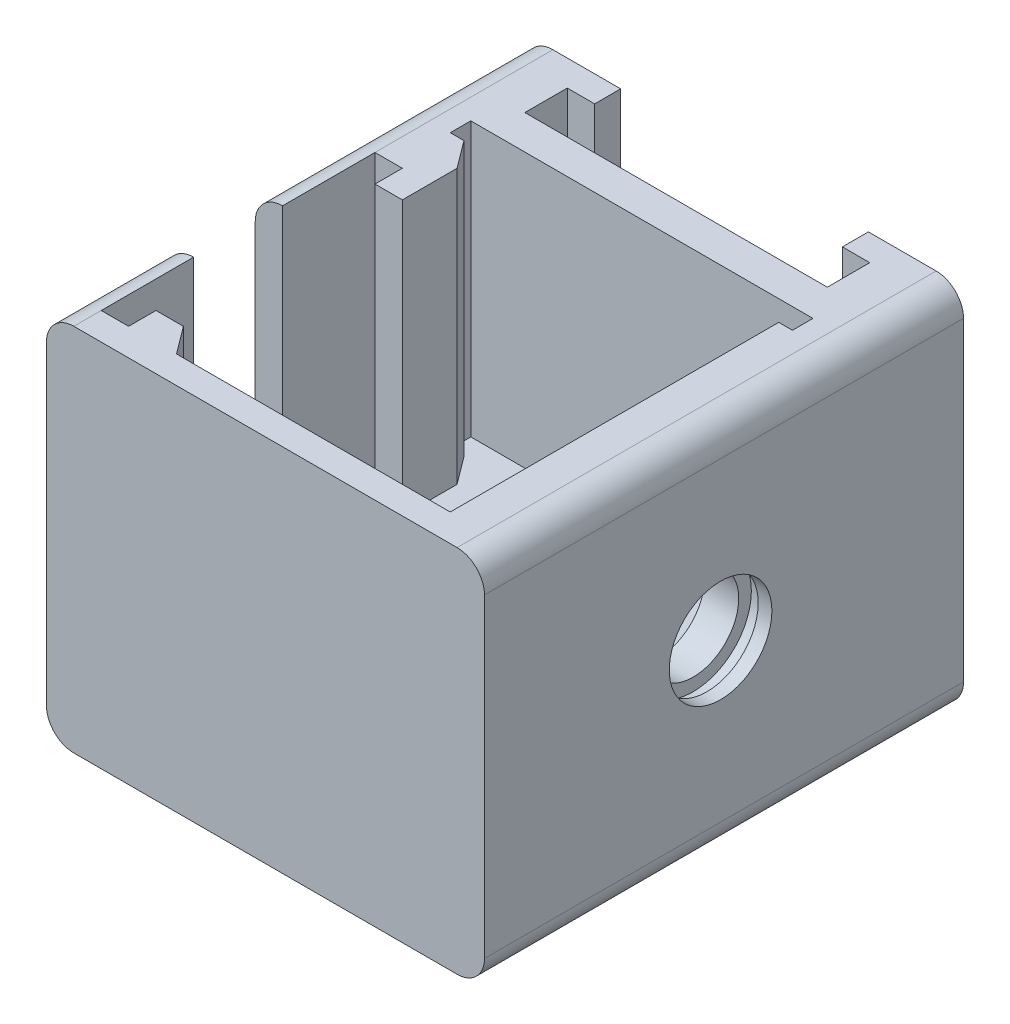
SolidWorks part; units mm, degrees
material "UNOBTANIUM"
ref_plane "Top Plane" through (0, 0, 0) normal (0, 0, 1) x (1, 0, 0)
ref_plane "Right Plane" through (0, 0, 0) normal (0, 1, 0) x (1, 0, 0)
ref_plane "Front Plane" through (0, 0, 0) normal (1, 0, 0) x (0, 0, -1)
ref_axis "x-axis" through (-17.6, 0, 0) along (1, 0, 0)
ref_axis "y-axis" through (0, -14.85, 0) along (0, 1, 0)
ref_axis "z-axis" through (0, 0, 36.75) along (0, 0, -1)
sketch "Sketch1" plane through (0, 0, 0) normal (0, 0, 1) x (1, 0, 0)
  line L1 (-16, 13.5) -> (16, 13.5)
  line L2 (-16, 13.5) -> (-16, -13.5)
  line L3 (-16, -13.5) -> (16, -13.5)
  line L4 (16, 13.5) -> (16, -13.5)
  line L5 (-16, 13.5) -> (16, -13.5) construction
  line L6 (-16, -13.5) -> (16, 13.5) construction
  point P0 (0, 0)
  dimension "D1" = 32
  dimension "D2" = 27
extrude "Boss-Extrude1" add sketch "Sketch1" along normal blind 35
fillet "Fillet1" radius 2 4 edges at (16, -13.5, 17.5) (16, 13.5, 17.5) (-16, -13.5, 17.5) (-16, 13.5, 17.5)
sketch "Sketch2" plane through (0, -13.5, 0) normal (0, -1, 0) x (1, 0, 0)
  line L0 (-9.05, 0) -> (-9.05, 1.9)
  line L1 (-14, 0) -> (14, 0) construction
  line L2 (-9.05, 1.9) -> (-11.05, 1.9)
  line L3 (-11.05, 1.9) -> (-11.05, 5)
  line L4 (-11.05, 5) -> (11.05, 5)
  line L5 (11.05, 5) -> (11.05, 1.9)
  line L6 (11.05, 1.9) -> (9.05, 1.9)
  line L7 (9.05, 1.9) -> (9.05, 0)
  line L9 (-9.05, 0) -> (9.05, 0)
  point P4 (0, 0)
  dimension "D1" = 18.1
  dimension "D2" = 1.9
  dimension "D3" = 3.1
  dimension "D4" = 22.1
extrude "Cut-Extrude1" cut sketch "Sketch2" against normal through all both and the other way through all
sketch "Sketch3" plane through (0, -13.5, 0) normal (0, -1, 0) x (1, 0, 0)
  line L0 (-9.05, 0) -> (-9.05, 1.9)
  line L1 (-9.05, 1.9) -> (-11.05, 1.9)
  line L2 (-11.05, 1.9) -> (-11.05, 5)
  line L3 (-11.05, 5) -> (11.05, 5)
  line L4 (11.05, 5) -> (11.05, 1.9)
  line L5 (11.05, 1.9) -> (9.05, 1.9)
  line L6 (9.05, 1.9) -> (9.05, 0)
  line L7 (9.05, 0) -> (-9.05, 0)
extrude "Boss-Extrude2" add sketch "Sketch3" against normal blind 7
sketch "Sketch4" plane through (0, 0, 1.9) normal (0, 0, -1) x (-1, 0, 0)
  line L1 (-9.05, 6.5) -> (-9.05, 5.5)
  line L2 (-9.05, 13.5) -> (-9.05, -6.5) construction
  arc A0 (-9.05, 6.5) -> (-9.05, 5.5) centre (-9.425, 6) cw
  dimension "D1" = 0.625
  dimension "D2" = 0.25
  dimension "D3" = 7
extrude "Boss-Extrude3" add sketch "Sketch4" along normal up to surface (1.9 mm away) up to face at (0, 1.1667, 0)
mirror "Mirror1" about plane through (0, 0, 0) normal (1, 0, 0) of "Boss-Extrude3"
sketch "Sketch5" plane through (0, 0, 0) normal (0, 0, -1) x (-1, 0, 0)
  line L0 (9.05, -6.5) -> (-9.05, -6.5) construction
  line L1 (-1, -6.5) -> (1, -6.5)
  line L2 (-1, -6.5) -> (-1, -13.5)
  line L3 (-1, -13.5) -> (1, -13.5)
  line L4 (1, -6.5) -> (1, -13.5)
  line L5 (14, -13.5) -> (-14, -13.5) construction
  point P8 (0, -6.5)
  dimension "D1" = 2
extrude "Cut-Extrude2" cut sketch "Sketch5" against normal offset from surface (33 mm away) 2 up to face at (0, 0, 35)
sketch "Sketch6" plane through (0, 13.5, 0) normal (0, 1, 0) x (1, 0, 0)
  line L0 (-12.5, -7.5) -> (-12.5, -9)
  line L1 (-12.5, -9) -> (-11.5, -9)
  line L2 (-11.5, -9) -> (-11.5, -33)
  line L3 (-11.5, -33) -> (11.5, -33)
  line L4 (11.5, -33) -> (11.5, -9)
  line L5 (11.5, -9) -> (12.5, -9)
  line L6 (12.5, -9) -> (12.5, -7.5)
  line L7 (12.5, -7.5) -> (-12.5, -7.5)
  line L8 (11.05, -5) -> (-11.05, -5) construction
  line L9 (0, -7.5) -> (0, -5) construction
  line L10 (14, -35) -> (-14, -35) construction
  dimension "D1" = 2.5
  dimension "D2" = 1.5
  dimension "D3" = 1
  dimension "D4" = 25
  dimension "D5" = 2
extrude "Cut-Extrude3" cut sketch "Sketch6" against normal up to surface (20 mm away) up to face at (7.0333, -6.5, 2.3)
sketch "Sketch7" plane through (0, -13.5, 0) normal (0, -1, 0) x (1, 0, 0)
  line L0 (1, 0) -> (14, 0) construction
  line L1 (1, 0) -> (-1, 0)
  line L2 (1, 0) -> (1, 33)
  line L3 (1, 33) -> (-1, 33)
  line L4 (-1, 0) -> (-1, 33)
  line L5 (1, 33) -> (1, 0) construction
extrude "Boss-Extrude4" add sketch "Sketch7" against normal blind 0.25
fillet "Fillet2" radius 6 1 edges at (0, -13.25, 33)
ref_axis "Axis1" through (63.07, 0, 17.75) along (-1, 0, 0)
ref_plane "Plane1" through (0, 0, 17.75) normal (0, 0, -1) x (-1, 0, 0)
sketch "Sketch9" plane through (0, 0, 17.75) normal (0, 0, -1) x (-1, 0, 0)
  line L0 (-15, 4.25) -> (-14, 4.25)
  line L1 (-16, -11.5) -> (-16, 11.5) construction
  line L2 (-14, 4.25) -> (-14, 3.325)
  line L3 (-14, 3.325) -> (-11.5, 3.325)
  line L4 (-11.5, 3.325) -> (-11.5, 0)
  line L5 (-63.07, 0) -> (46.93, 0) construction
  line L6 (-11.5, 0) -> (-16, 0)
  line L8 (-16, 0) -> (-0.664, 0) construction
  line L9 (-11.5, -6.5) -> (-11.5, 13.5) construction
  line L10 (-15, 4.25) -> (-15, 3.75)
  line L11 (-15, 3.75) -> (-16, 3.75)
  line L12 (-16, 3.75) -> (-16, 0)
  dimension "D1" = 6.65
  dimension "D2" = 8.5
  dimension "D3" = 1
  dimension "D4" = 1
  dimension "D5" = 7.5
revolve "Cut-Revolve1" cut sketch "Sketch9" angle 360 about L8
sketch "Sketch10" plane through (0, 13.5, 0) normal (0, 1, 0) x (1, 0, 0)
  line L0 (11.5, -31) -> (13.5, -31)
  line L1 (11.5, -9) -> (11.5, -33) construction
  line L2 (13.5, -31) -> (13.5, -33)
  line L3 (13.5, -33) -> (11.5, -33)
  line L4 (11.5, -33) -> (11.5, -31)
  dimension "D1" = 2
  dimension "D2" = 2
extrude "Cut-Extrude4" [suppressed] cut sketch "Sketch10" against normal up to surface (20 mm away)
mirror "Mirror2" [suppressed] about plane through (0, 0, 0) normal (1, 0, 0)
sketch "Sketch11" plane through (-16, 0, 44) normal (1, 0, 0) x (0, 0, -1)
  line L0 (21, 23) -> (21, 0) construction
  line L4 (24.25, 23) -> (24.25, 0)
  line L5 (17.75, 23) -> (17.75, 0)
  line L6 (9, 11.5) -> (44, 11.5) construction
  line L7 (21, 0) -> (44, 0) construction
  line L8 (9, 11.5) -> (9, -11.5) construction
  arc A2 (24.25, 23) -> (17.75, 23) centre (21, 23) ccw
  arc A3 (17.75, 0) -> (24.25, 0) centre (21, 0) ccw
  point P2 (21, 11.5)
  dimension "D1" = 6.5
  dimension "D2" = 12
extrude "Cut-Extrude5" cut sketch "Sketch11" along normal up to surface (4.5 mm away) up to face at (-11.5, 3.5, 21)
sketch "Sketch14" plane through (0, 13.5, 0) normal (0, 1, 0) x (1, 0, 0)
  line L0 (-11.5, -9) -> (-11.5, -19.75) construction
  line L1 (-11.5, -13) -> (-14, -13)
  line L2 (-11.5, -13) -> (-11.5, -33)
  line L3 (-11.5, -33) -> (-14, -33)
  line L4 (-14, -13) -> (-14, -33)
  line L5 (-16, -35) -> (-16, -26.25) construction
  line L6 (-11.5, -26.25) -> (-11.5, -19.75) construction
  point P12 (-11.5, -23)
  dimension "D1" = 2
extrude "Cut-Extrude6" cut sketch "Sketch14" against normal up to surface (20 mm away) up to face at (-8.3333, -6.5, 16.5)
sketch "Sketch16" plane through (0, 13.5, 0) normal (0, 1, 0) x (1, 0, 0)
  line L1 (-12, -11) -> (-10, -11)
  line L2 (-12, -11) -> (-12, -15)
  line L3 (-12, -15) -> (-10, -15)
  line L4 (-10, -11) -> (-10, -15)
  line L5 (-14, -33) -> (-14, -13) construction
  line L6 (-12, -33) -> (-12, -31)
  line L7 (-14, -33) -> (11.5, -33) construction
  line L8 (-12, -31) -> (-10, -31)
  line L9 (-10, -31) -> (-10, -33)
  line L10 (-10, -33) -> (-12, -33)
  line L11 (-12.5, -9) -> (-11.5, -9) construction
  line L13 (-11.5, -13) -> (-14, -13) construction
  line L14 (-14, -13) -> (-14, -19.75) construction
  dimension "D1" = 4
  dimension "D2" = 2
  dimension "D3" = 2
  dimension "D4" = 2
  dimension "D5" = 2
extrude "Boss-Extrude5" add sketch "Sketch16" against normal up to surface (20 mm away) up to face at (8.3333, -6.5, 16.5)
sketch "Sketch20" plane through (0, 13.5, 0) normal (0, 1, 0) x (1, 0, 0)
  line L0 (-11.5, -9) -> (-10, -11)
  line L1 (-10, -11) -> (-11.5, -11)
  line L2 (-11.5, -11) -> (-11.5, -9)
  line L3 (-10, -31) -> (-8.5, -33)
  line L4 (-1, -33) -> (-10, -33) construction
  line L5 (-8.5, -33) -> (-10, -33)
  line L6 (-10, -33) -> (-10, -31)
extrude "Boss-Extrude6" add sketch "Sketch20" against normal up to surface (20 mm away) up to face at (8.3333, -6.5, 16.5)
